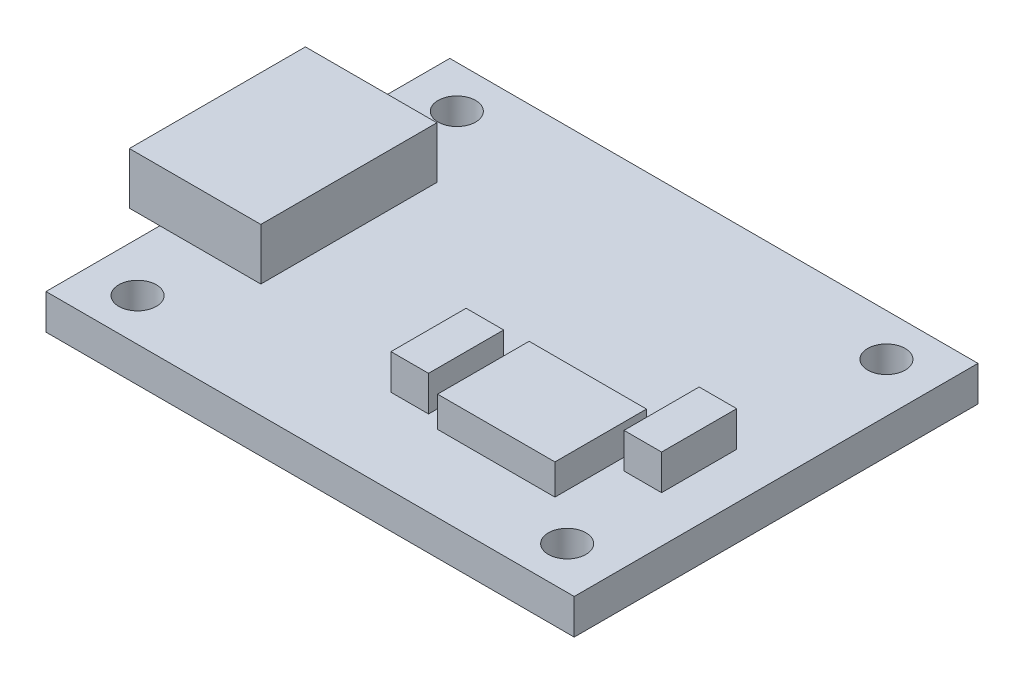
SolidWorks part; units mm, degrees
ref_plane "Front Plane" through (0, 0, 0) normal (0, 0, 1) x (1, 0, 0)
ref_plane "Top Plane" through (0, 0, 0) normal (0, 1, 0) x (1, 0, 0)
ref_plane "Right Plane" through (0, 0, 0) normal (1, 0, 0) x (0, 0, -1)
sketch "Sketch1" plane through (0, 0, 0) normal (0, 1, 0) x (1, 0, 0)
  line L1 (11.25, 8.6) -> (-11.25, 8.6)
  line L2 (11.25, 8.6) -> (11.25, -8.6)
  line L3 (11.25, -8.6) -> (-11.25, -8.6)
  line L4 (-11.25, 8.6) -> (-11.25, -8.6)
  line L5 (11.25, 8.6) -> (-11.25, -8.6) construction
  line L6 (11.25, -8.6) -> (-11.25, 8.6) construction
  point P0 (0, 0)
  dimension "D1" = 22.5
  dimension "D2" = 17.2
extrude "Boss-Extrude1" add sketch "Sketch1" along normal blind 1.5
sketch "Sketch2" plane through (0, 1.5, 0) normal (0, 1, 0) x (1, 0, 0)
  line L1 (7.6826, -2.9107) -> (9.2826, -2.9107)
  line L2 (7.6826, -2.9107) -> (7.6826, 0.2893)
  line L3 (7.6826, 0.2893) -> (9.2826, 0.2893)
  line L4 (9.2826, -2.9107) -> (9.2826, 0.2893)
  line L5 (2.1752, -5.3463) -> (7.1752, -5.3463)
  line L6 (2.1752, -5.3463) -> (2.1752, -1.4463)
  line L7 (2.1752, -1.4463) -> (7.1752, -1.4463)
  line L8 (7.1752, -5.3463) -> (7.1752, -1.4463)
  line L9 (-0.1851, -1.7702) -> (1.4149, -1.7702)
  line L10 (-0.1851, -1.7702) -> (-0.1851, -4.9702)
  line L11 (-0.1851, -4.9702) -> (1.4149, -4.9702)
  line L12 (1.4149, -1.7702) -> (1.4149, -4.9702)
  point P12 (2.476, -1.5157)
  point P13 (-0.1851, -1.7471)
  point P14 (2.1752, -1.4463)
  dimension "D1" = 1.6
  dimension "D2" = 3.2
  dimension "D3" = 5
  dimension "D4" = 3.9
extrude "Boss-Extrude2" add sketch "Sketch2" along normal blind 1.5 contours L12 L9 L10 L11 | L1 L4 L3 L2 region at (8.4826, 1.5, 1.3107) region at (0.6149, 1.5, 3.3702)
extrude "Boss-Extrude3" add sketch "Sketch2<3>" along normal blind 1.3 contours L6 L7 L8 L5
sketch "Sketch2<3>" plane through (0, 1.5, 0) normal (0, 1, 0) x (1, 0, 0) same geometry as "Sketch2"
sketch "Sketch3" plane through (0, 1.5, 0) normal (0, 1, 0) x (1, 0, 0)
  line L0 (-11.25, 8.6) -> (-11.25, -8.6) construction
  line L1 (-6.95, -3.75) -> (-12.55, -3.75)
  line L2 (-6.95, -3.75) -> (-6.95, 3.75)
  line L3 (-6.95, 3.75) -> (-12.55, 3.75)
  line L4 (-12.55, -3.75) -> (-12.55, 3.75)
  line L5 (-6.95, -3.75) -> (-12.55, 3.75) construction
  line L6 (-6.95, 3.75) -> (-12.55, -3.75) construction
  point P0 (-9.75, 0)
  point P5 (0, 0)
  dimension "D1" = 5.6
  dimension "D2" = 7.5
  dimension "D3" = 1.3
extrude "Boss-Extrude4" add sketch "Sketch3" along normal blind 2.2
sketch "Sketch4" plane through (0, 0, 0) normal (0, 1, 0) x (1, 0, 0)
  line L0 (11.25, 0) -> (-11.25, 0) construction
  line L1 (11.25, -8.6) -> (11.25, 8.6) construction
  line L2 (-11.25, 8.6) -> (-11.25, -8.6) construction
  line L3 (-11.25, -8.6) -> (11.25, -8.6) construction
  line L4 (-11.25, -3.75) -> (-11.25, -8.6) construction
  line L5 (0, 8.6) -> (0, -8.6) construction
  line L6 (11.25, 8.6) -> (-11.25, 8.6) construction
  circle A0 centre (-9.15, 6.8) radius 0.8
  circle A1 centre (-9.15, -6.8) radius 0.8
  circle A2 centre (9.15, -6.8) radius 0.8
  circle A3 centre (9.15, 6.8) radius 0.8
  dimension "D1" = 12
  dimension "D2" = 1
  dimension "D3" = 1.3
extrude "Cut-Extrude1" cut sketch "Sketch4" along normal through all
